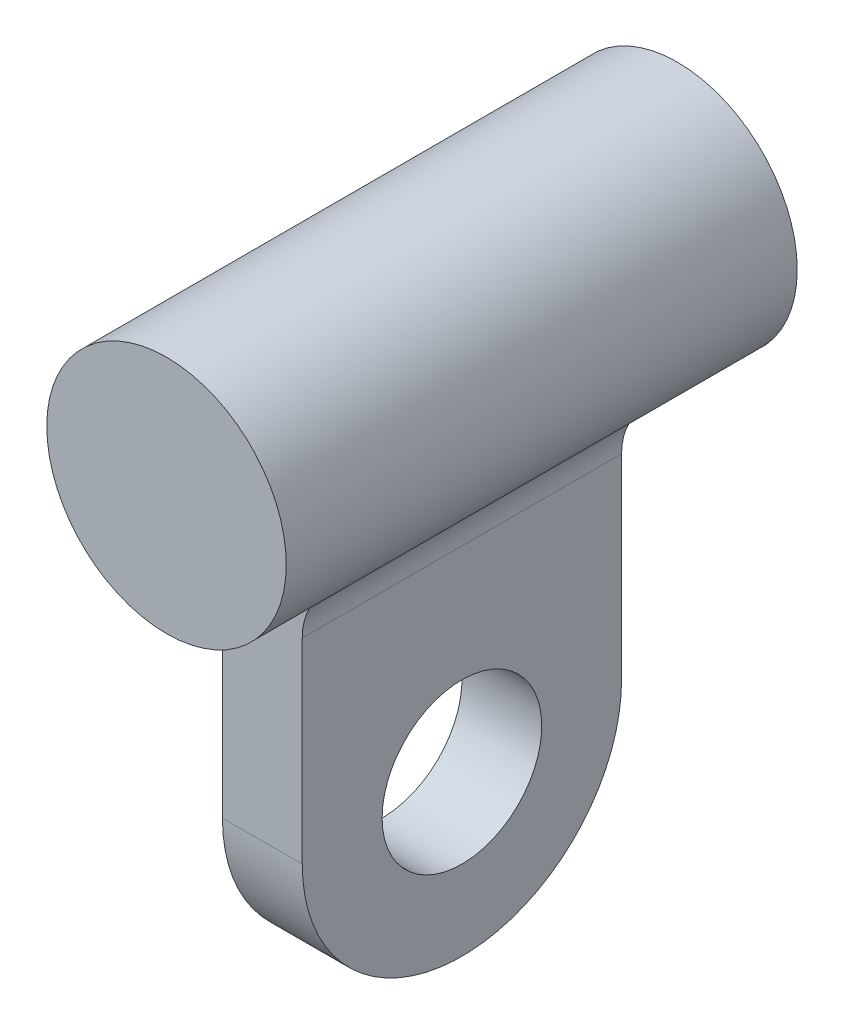
SolidWorks part; units mm, degrees
ref_plane "Front Plane" through (0, 0, 0) normal (0, 0, 1) x (1, 0, 0)
ref_plane "Top Plane" through (0, 0, 0) normal (0, 1, 0) x (1, 0, 0)
ref_plane "Right Plane" through (0, 0, 0) normal (1, 0, 0) x (0, 0, -1)
sketch "Sketch1" plane through (0, 0, 0) normal (0, 0, 1) x (1, 0, 0)
  circle A0 centre (-80.7816, -8.89) radius 4.7625
  dimension "D1" = 9.525
extrude "Boss-Extrude1" add sketch "Sketch1" along normal blind 20.32
ref_plane "Plane1" through (0, -10, 0) normal (0, 1, 0) x (1, 0, 0)
sketch "Sketch2" plane through (0, -10, 0) normal (0, 1, 0) x (1, 0, 0)
  line L0 (-74.4316, -20.32) -> (-86.9497, -20.32) construction
  line L1 (-79.1941, -3.81) -> (-82.3691, -3.81)
  line L2 (-79.1941, -3.81) -> (-79.1941, -16.51)
  line L3 (-79.1941, -16.51) -> (-82.3691, -16.51)
  line L4 (-82.3691, -3.81) -> (-82.3691, -16.51)
  line L8 (-76.0191, 0) -> (-76.0191, -20.32) construction
  dimension "D1" = 3.175
  dimension "D2" = 12.7
  dimension "D3" = 3.81
  dimension "D4" = 3.175
extrude "Boss-Extrude2" add sketch "Sketch2" against normal blind 19.05
sketch "Sketch3" plane through (-82.3691, 0, 0) normal (-1, 0, 0) x (0, 0, 1)
  line L0 (3.81, -29.05) -> (3.81, -13.3801) construction
  line L1 (3.81, -29.05) -> (16.51, -29.05) construction
  line L2 (16.51, -29.05) -> (16.51, -13.3801) construction
  line L3 (3.81, -22.7) -> (3.81, -29.05)
  line L4 (3.81, -29.05) -> (10.16, -29.05)
  line L5 (10.16, -29.05) -> (16.51, -29.05)
  line L6 (16.51, -29.05) -> (16.51, -22.7)
  arc A0 (3.81, -22.7) -> (16.51, -22.7) centre (10.16, -22.7) ccw
  line M2 (3.81, -13.3801) -> (3.81, -29.05)
  line M3 (3.81, -29.05) -> (16.51, -29.05)
  line M4 (16.51, -29.05) -> (16.51, -13.3801)
extrude "Cut-Extrude1" cut sketch "Sketch3" against normal through all contours A0 M3 M4 | A0 M2 M3 region at (-82.3691, -27.6316, 5.2284) region at (-82.3691, -27.6316, 15.0916)
sketch "Sketch4" plane through (-82.3691, 0, 0) normal (-1, 0, 0) x (0, 0, 1)
  circle A0 centre (10.16, -22.7) radius 3.175
  dimension "D1" = 6.35
extrude "Cut-Extrude2" cut sketch "Sketch4" against normal through all
fillet "Fillet1" radius 2.54 2 edges at (-79.1941, -13.3801, 10.16) (-82.3691, -13.3801, 10.16)
